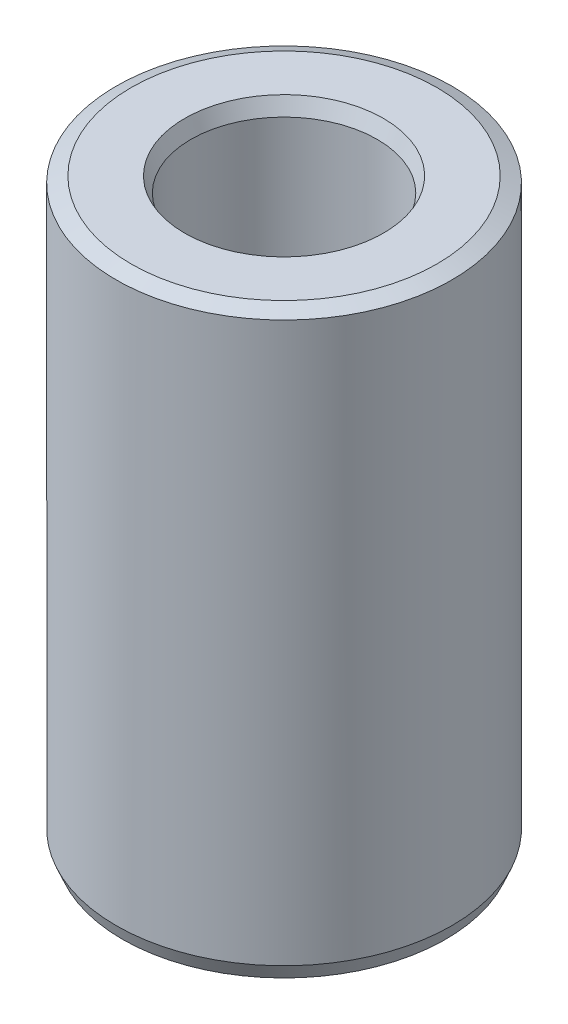
SolidWorks part; units mm, degrees
ref_plane "Front Plane" through (0, 0, 0) normal (0, 0, 1) x (1, 0, 0)
ref_plane "Top Plane" through (0, 0, 0) normal (0, 1, 0) x (1, 0, 0)
ref_plane "Right Plane" through (0, 0, 0) normal (1, 0, 0) x (0, 0, -1)
sketch "Sketch1" plane through (0, 0, 0) normal (0, 1, 0) x (1, 0, 0)
  circle A0 centre (0, 0) radius 52.5
  dimension "SLEEVE_OD" = 105
extrude "Boss-Extrude1" add sketch "Sketch1" along normal blind 181.5383
sketch "Sketch2" plane through (0, 0, 0) normal (0, 1, 0) x (1, 0, 0)
  circle A0 centre (0, 0) radius 29.134
  dimension "BORE_D" = 58.2679
extrude "Cut-Extrude1" cut sketch "Sketch2" along normal through all
chamfer "Chamfer1" distance 1.9582 angle 67.357 4 edges at (0, 181.5383, 29.134) (0, 0, 29.134) (0, 0, 52.5) (0, 181.5383, 52.5) first distance on face at (0, 181.5383, 29.134) first distance on face at (0, 0, 29.134) first distance on face at (0, 181.5383, 52.5)
